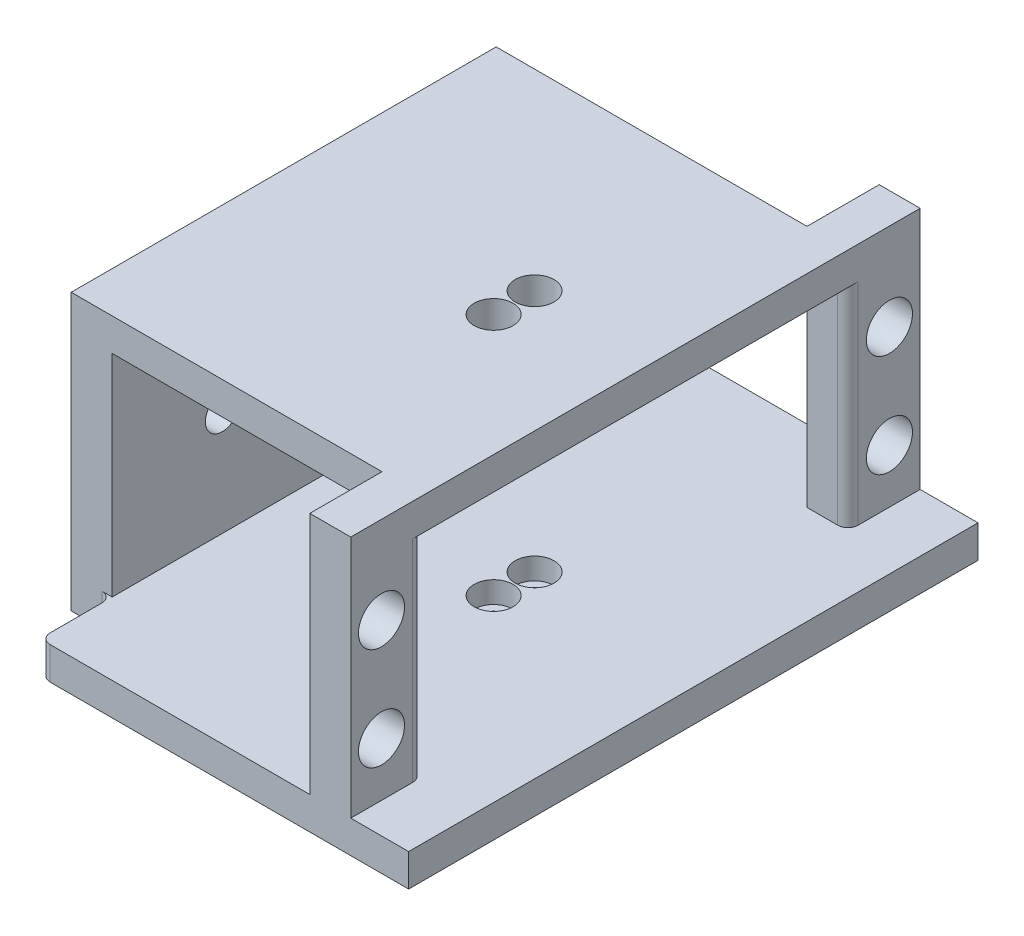
SolidWorks part; units mm, degrees
ref_plane "Front Plane" through (0, 0, 0) normal (0, 0, 1) x (1, 0, 0)
ref_plane "Top Plane" through (0, 0, 0) normal (0, 1, 0) x (1, 0, 0)
ref_plane "Right Plane" through (0, 0, 0) normal (1, 0, 0) x (0, 0, -1)
sketch "Sketch1" plane through (0, 0, 0) normal (0, 1, 0) x (1, 0, 0)
  line L1 (-20, 27.8) -> (20, 27.8)
  line L2 (-20, 27.8) -> (-20, -27.8)
  line L3 (-20, -27.8) -> (20, -27.8)
  line L4 (20, 27.8) -> (20, -27.8)
  line L5 (-20, 27.8) -> (20, -27.8) construction
  line L6 (-20, -27.8) -> (20, 27.8) construction
  point P0 (0, 0)
  dimension "D1" = 55.6
  dimension "D2" = 40
extrude "Boss-Extrude1" add sketch "Sketch1" along normal blind 3.175
sketch "Sketch2" plane through (0, 3.175, 0) normal (0, 1, 0) x (1, 0, 0)
  line L0 (-20, 27.8) -> (-20, -27.8) construction
  line L1 (-16, 20.75) -> (-20, 20.75)
  line L2 (-16, 20.75) -> (-16, -20.75)
  line L3 (-16, -20.75) -> (-20, -20.75)
  line L4 (-20, 20.75) -> (-20, -20.75)
  line L5 (-16, 20.75) -> (-20, -20.75) construction
  line L6 (-16, -20.75) -> (-20, 20.75) construction
  line L8 (-20, -27.8) -> (20, -27.8) construction
  line L9 (-20, 0) -> (65.8452, 0) construction
  line L12 (10.35, 27.8) -> (10.35, 20.75)
  line L13 (14.35, -27.8) -> (10.35, -27.8)
  line L14 (14.35, -27.8) -> (14.35, -20.75)
  line L15 (14.35, -20.75) -> (10.35, -20.75)
  line L16 (10.35, -27.8) -> (10.35, -20.75)
  line L17 (14.35, 20.75) -> (10.35, 20.75)
  line L18 (14.35, 27.8) -> (14.35, 20.75)
  line L19 (14.35, 27.8) -> (10.35, 27.8)
  line L27 (-5.55, 20.1) -> (14.25, 20.1) construction
  line L28 (-5.55, -20.1) -> (14.25, -20.1) construction
  line L30 (20, -27.8) -> (20, 27.8) construction
  point P0 (-18, 0)
  dimension "D1" = 4
  dimension "D4" = 4
  dimension "D6" = 7.05
  dimension "D9" = 41.5
  dimension "D2" = 41.5
  dimension "D3" = 0.65
  dimension "D7" = 0.65
  dimension "D5" = 5.65
extrude "Boss-Extrude2" add sketch "Sketch2" along normal blind 20.6
sketch "Sketch3" plane through (0, 23.775, 0) normal (0, 1, 0) x (1, 0, 0)
  line L0 (-20, 20.75) -> (10.35, 20.75)
  line L16 (14.35, -27.8) -> (10.35, -27.8)
  line L17 (10.35, -27.8) -> (10.35, -20.75)
  line L18 (10.35, -20.75) -> (-20, -20.75)
  line L19 (-20, -20.75) -> (-20, 20.75)
  line L20 (10.35, 20.75) -> (10.35, 27.8)
  line L21 (10.35, 27.8) -> (14.35, 27.8)
  line L22 (14.35, 27.8) -> (14.35, -27.8)
extrude "Boss-Extrude3" add sketch "Sketch3" along normal blind 3.175
sketch "Sketch5" plane through (14.35, 0, 0) normal (1, 0, 0) x (0, 0, -1)
  line L0 (-27.8, 26.95) -> (-27.8, 3.175) construction
  line L1 (-27.8, 3.175) -> (-20.75, 3.175) construction
  line L2 (0, 0) -> (0, 26.95) construction
  line L3 (-27.8, 26.95) -> (27.8, 26.95) construction
  circle A0 centre (-24.8, 8.425) radius 2.25
  circle A1 centre (-24.8, 18.425) radius 2.25
  circle A2 centre (24.8, 18.425) radius 2.25
  circle A3 centre (24.8, 8.425) radius 2.25
  dimension "D1" = 4.5
  dimension "D3" = 5.25
  dimension "D2" = 3
  dimension "D4" = 10
extrude "Cut-Extrude2" cut sketch "Sketch5" against normal up to surface (4 mm away) up to face at (10.35, 16.805, 23.57)
sketch "Sketch6" plane through (-20, 0, 0) normal (-1, 0, 0) x (0, 0, 1)
  circle A0 centre (10, 13.43) radius 1.65
  dimension "D1" = 3.3
extrude "Cut-Extrude3" cut sketch "Sketch6" against normal up to surface (4 mm away) contours A0 up to face at (-16, 13.475, 0)
fillet "Fillet1" radius 1 2 edges at (14.35, 13.475, 20.75) (14.35, 13.475, -20.75)
sketch "Sketch7" plane through (0, 3.175, 0) normal (0, 1, 0) x (1, 0, 0)
  line L1 (-20, -27.8) -> (-16, -27.8)
  line L2 (-20, -27.8) -> (-20, -20.75)
  line L3 (-20, -20.75) -> (-16, -20.75)
  line L4 (-16, -27.8) -> (-16, -20.75)
  line L5 (-20, 27.8) -> (-16, 27.8)
  line L6 (-20, 27.8) -> (-20, 20.75)
  line L7 (-20, 20.75) -> (-16, 20.75)
  line L8 (-16, 27.8) -> (-16, 20.75)
extrude "Cut-Extrude4" cut sketch "Sketch7" against normal up to surface (3.175 mm away) up to face at (0, 0, 0)
fillet "Fillet2" radius 1 4 edges at (-16, 1.5875, 27.8) (-16, 1.5875, 20.75) (-16, 1.5875, -20.75) (-16, 1.5875, -27.8)
sketch "Sketch8" plane through (0, 0, 0) normal (0, -1, 0) x (1, 0, 0)
  line L0 (-20, 0) -> (20, 0) construction
  line L1 (-20, -20.75) -> (-20, 20.75) construction
  line L2 (20, 27.8) -> (20, -27.8) construction
  line L3 (2.5, 27.8) -> (2.5, -27.8) construction
  line L5 (-15, 27.8) -> (20, 27.8) construction
  line L6 (20, -27.8) -> (-15, -27.8) construction
  circle A0 centre (2.5, 0) radius 4 construction
  circle A1 centre (2.5, -2) radius 1.1
  circle A2 centre (2.5, 2) radius 1.1
  dimension "D1" = 8
  dimension "D2" = 2.2
  dimension "D3" = 2
  dimension "D4" = 2
extrude "Cut-Extrude6" cut sketch "Sketch8" against normal up to surface (3.175 mm away) up to face at (0.2688, 3.175, 0)
sketch "Sketch9" plane through (0, 3.175, 0) normal (0, 1, 0) x (1, 0, 0)
  circle A0 centre (2.5, -2) radius 1.9
  circle A1 centre (2.5, 2) radius 1.9
  dimension "D1" = 3.8
extrude "Cut-Extrude7" cut sketch "Sketch9" against normal blind 2.1
sketch "Sketch11" plane through (0, 3.175, 0) normal (0, 1, 0) x (1, 0, 0)
  circle A0 centre (2.5, -2) radius 1.9
  circle A1 centre (2.5, 2) radius 1.9
  circle A2 centre (2.5, 2) radius 1.9 construction
  circle A3 centre (2.5, -2) radius 1.9 construction
  point P6 (8.6617, -6.8256)
  dimension "D1" = 3.8
  dimension "D2" = 0
  dimension "D3" = 0
  dimension "D4" = 0
  dimension "D5" = 0
extrude "Cut-Extrude9" cut sketch "Sketch11" along normal up to surface (23.775 mm away) up to face at (3.7625, 26.95, 0)
equation "\"D4@Sketch2\"=\"D1@Sketch2\""
equation "\"D2@Sketch2\"=\"D9@Sketch2\""
